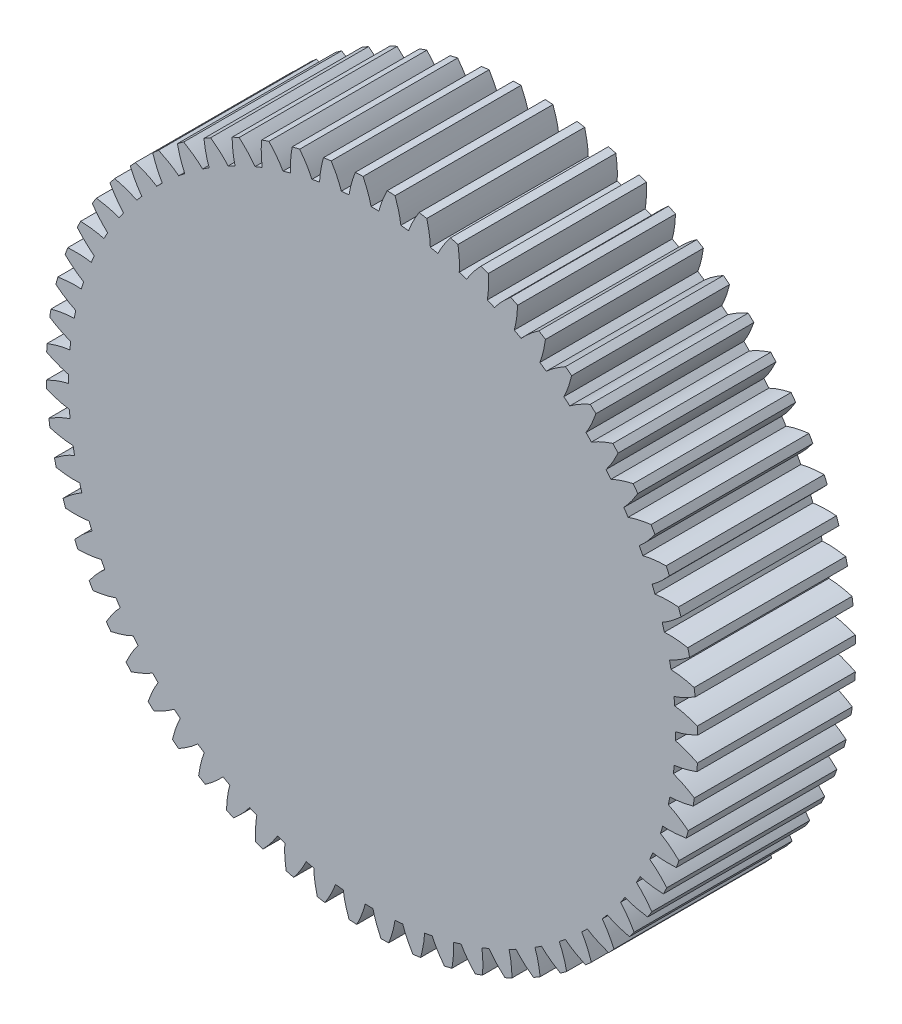
SolidWorks part; units mm, degrees
note: '?' marks a value the reader was unsure of.
ref_plane "Front" through (0, 0, 0) normal (0, 0, 1) x (1, 0, 0)
ref_plane "Top" through (0, 0, 0) normal (0, 1, 0) x (1, 0, 0)
ref_plane "Right" through (0, 0, 0) normal (1, 0, 0) x (0, 0, -1)
ref_axis "Axis1" through (0, 0, -80.9) along (0, 0, 1)?
sketch "Sketch1" plane through (0, 0, 0) normal (0, 0, 1) x (1, 0, 0)
  circle A0 centre (0, 0) radius 26.1937
  dimension "D1" = 52.3875
extrude "Boss-Extrude1" add sketch "Sketch1" against normal blind 12.7
sketch "Sketch2" plane through (0, 0, 0) normal (0, 0, 1) x (1, 0, 0)
  line L0 (12.2039, 0) -> (23.8682, 0)
  line L1 (0, 0) -> (-7.9817, 0.0769) construction
  line L2 (12.2016, -0.2353) -> (23.8638, -0.4601)
  circle A0 centre (0, 0) radius 25.4 construction
  circle A1 centre (0, 0) radius 23.8682 construction
  circle A2 centre (0, 0) radius 24.4078 construction
  arc A3 (12.2016, -0.2353) -> (12.2039, 0) centre (0, 0) ccw
  spline S0 degree 4 poles (23.8682, 0) (23.905, 0.0012) (23.9784, 0.0057) (24.1835, 0.03) (24.5698, 0.1058) (25.1502, 0.2727) (25.9221, 0.5776) (26.8744, 1.0589) (27.9314, 1.7266) (29.0206, 2.5635) (30.1105, 3.5653) (31.1179, 4.6498) (32.0445, 5.8037) (32.9341, 7.0767) (33.9284, 8.7227) (34.9504, 10.777) (35.9105, 13.2637) (36.6996, 16.1187) (37.2234, 19.0334) (37.4944, 21.9819) (37.5245, 24.9424) (37.3256, 27.8961) (36.9613, 30.4603) (36.5566, 32.4541) (36.2047, 33.8902) (35.9161, 34.9617) (35.6044, 36.0247) (35.2615, 37.0827) (34.8932, 38.1244) (34.5635, 38.9946) (34.2959, 39.6709) (34.0281, 40.3138) (33.8041, 40.8352) (33.5399, 41.426) (33.3651, 41.8069) (33.077, 42.4195) (32.8445, 42.8918) (32.5584, 43.4637) (32.2947, 43.9691) (32.0061, 44.5115) (31.7241, 45.0221) (31.4994, 45.421) (31.353, 45.6739) (31.277, 45.8051) knots 0 0 0 0 0 0.002802 0.005604 0.015718 0.02996 0.048734 0.068727 0.096889 0.125051 0.153212 0.181374 0.209535 0.237696 0.271429 0.327752 0.384075 0.440398 0.496721 0.553044 0.609367 0.66569 0.722013 0.750174 0.764255 0.778336 0.806497 0.834659 0.84874 0.86282 0.876901 0.890982 0.900036 0.909091 0.920455 0.931818 0.943182 0.954545 0.965909 0.977273 0.988636 1 1 1 1 1 construction
  spline S1 degree 4 poles (23.8682, 0) (23.905, 0.0012) (23.9784, 0.0057) (24.1835, 0.03) (24.5698, 0.1058) (25.1502, 0.2727) (25.9221, 0.5776) (26.8744, 1.0589) (27.9314, 1.7266) (29.0206, 2.5635) (30.1105, 3.5653) (31.1179, 4.6498) (32.0445, 5.8037) (32.9341, 7.0767) (33.9284, 8.7227) (34.9504, 10.777) (35.9105, 13.2637) (36.6996, 16.1187) (37.2234, 19.0334) (37.4944, 21.9819) (37.5245, 24.9424) (37.3256, 27.8961) (36.9613, 30.4603) (36.5566, 32.4541) (36.2047, 33.8902) (35.9161, 34.9617) (35.6044, 36.0247) (35.2615, 37.0827) (34.8932, 38.1244) (34.5635, 38.9946) (34.2959, 39.6709) (34.0281, 40.3138) (33.8041, 40.8352) (33.6088, 41.2719) (33.5189, 41.4704) (33.4739, 41.5686) knots 0 0 0 0 0 0.002802 0.005604 0.015718 0.02996 0.048734 0.068727 0.096889 0.125051 0.153212 0.181374 0.209535 0.237696 0.271429 0.327752 0.384075 0.440398 0.496721 0.553044 0.609367 0.66569 0.722013 0.750174 0.764255 0.778336 0.806497 0.834659 0.84874 0.86282 0.876901 0.890982 0.900036 0.909091 0.909091 0.909091 0.909091 0.909091
  spline S2 degree 4 poles (23.8638, -0.4601) (23.9005, -0.462) (23.9738, -0.468) (24.1784, -0.4962) (24.5632, -0.5794) (25.1403, -0.7574) (25.9062, -1.0772) (26.849, -1.5767) (27.8929, -2.2647) (28.9658, -3.1224) (30.0362, -4.1451) (31.0225, -5.2488) (31.9267, -6.4204) (32.7915, -7.7102) (33.7539, -9.3751) (34.7362, -11.4487) (35.6481, -13.9535) (36.382, -16.8231) (36.8496, -19.7474) (37.0636, -22.7006) (37.0367, -25.6611) (36.7809, -28.6104) (36.3672, -31.1671) (35.9242, -33.1528) (35.5446, -34.5818) (35.2354, -35.6476) (34.9033, -36.7044) (34.5401, -37.7555) (34.1518, -38.7899) (33.8053, -39.6537) (33.5248, -40.3246) (33.2446, -40.9622) (33.0106, -41.4793) (32.7351, -42.0649) (32.553, -42.4423) (32.2531, -43.0492) (32.0116, -43.517) (31.7145, -44.0833) (31.4411, -44.5835) (31.1421, -45.1202) (30.8503, -45.6253) (30.618, -46.0198) (30.4667, -46.2698) (30.3882, -46.3995) knots 0 0 0 0 0 0.002802 0.005604 0.015718 0.02996 0.048734 0.068727 0.096889 0.125051 0.153212 0.181374 0.209535 0.237696 0.271429 0.327752 0.384075 0.440398 0.496721 0.553044 0.609367 0.66569 0.722013 0.750174 0.764255 0.778336 0.806497 0.834659 0.84874 0.86282 0.876901 0.890982 0.900036 0.909091 0.920455 0.931818 0.943182 0.954545 0.965909 0.977273 0.988636 1 1 1 1 1 construction
  spline S3 degree 4 poles (23.8638, -0.4601) (23.9005, -0.462) (23.9738, -0.468) (24.1784, -0.4962) (24.5632, -0.5794) (25.1403, -0.7574) (25.9062, -1.0772) (26.849, -1.5767) (27.8929, -2.2647) (28.9658, -3.1224) (30.0362, -4.1451) (31.0225, -5.2488) (31.9267, -6.4204) (32.7915, -7.7102) (33.7539, -9.3751) (34.7362, -11.4487) (35.6481, -13.9535) (36.382, -16.8231) (36.8496, -19.7474) (37.0636, -22.7006) (37.0367, -25.6611) (36.7809, -28.6104) (36.3672, -31.1671) (35.9242, -33.1528) (35.5446, -34.5818) (35.2354, -35.6476) (34.9033, -36.7044) (34.5401, -37.7555) (34.1518, -38.7899) (33.8053, -39.6537) (33.5248, -40.3246) (33.2446, -40.9622) (33.0106, -41.4793) (32.807, -41.9121) (32.7132, -42.1088) (32.6663, -42.2062) knots 0 0 0 0 0 0.002802 0.005604 0.015718 0.02996 0.048734 0.068727 0.096889 0.125051 0.153212 0.181374 0.209535 0.237696 0.271429 0.327752 0.384075 0.440398 0.496721 0.553044 0.609367 0.66569 0.722013 0.750174 0.764255 0.778336 0.806497 0.834659 0.84874 0.86282 0.876901 0.890982 0.900036 0.909091 0.909091 0.909091 0.909091 0.909091
  dimension "D1" = 50.8
  dimension "D2" = 47.7364
  dimension "D3" = 48.8156
  dimension "D5" = 24.4078
  dimension "D4" = 0.552
extrude "Cut-Extrude1" cut sketch "Sketch2" against normal through all and the other way through all
pattern_circular "CirPattern1" count 64 over 360 about axis through (0, 0, -12.7) along (0, 0, 1) of "Cut-Extrude1"
sketch "Sketch3" plane through (0, 0, 0) normal (0, 0, 1) x (1, 0, 0)
  circle A1 centre (0, 0) radius 24.4078 construction
  circle A2 centre (0, 0) radius 24.4078
extrude "Boss-Extrude2" add sketch "Sketch3" against normal up to surface (12.7 mm away) up to face at (0, 0, -12.7)
sketch "Sketch4" plane through (0, 0, 0) normal (0, 0, 1) x (1, 0, 0)
  circle A0 centre (0, 0) radius 25.4 construction
  circle A1 centre (0, 0) radius 25.4
surface "Pitch Circle" sketch "Sketch4"
equation "\"P\"= \"P0\"'Diametral Pitch"
equation "\"N\"= \"N0\"'Number of Teeth"
equation "\"phi\"= \"phi0\"'Pressure Angle"
equation "\"a\"= 1 / \"P\"'Addendum"
equation "\"b\"= 1.25 / \"P\"'Dedendum"
equation "\"c\"= \"b\" - \"a\"'Clearance"
equation "\"dp\"= \"N\" / \"P\"'Pitch Circle Diameter"
equation "\"db\"= \"dp\" * cos ( \"phi\" )'Base Circle Diameter"
equation "\"alpha\"= sqr ( \"dp\" ^ 2 - \"db\" ^ 2 ) / \"db\" * 180deg / pi - \"phi\""
equation "\"D1@Sketch1\"=\"dp\"+2*\"a\""
equation "\"D3@Sketch2\"=\"dp\"-2*\"b\""
equation "\"D1@Sketch2\"=\"dp\""
equation "\"D2@Sketch2\"=\"db\""
equation "\"D4@Sketch2\"=360 / ( 4 * \"N\" ) - \"alpha\""
equation "\"D5@Sketch2\"=(\"dp\"-2*\"b\")/2"
equation "\"D1@CirPattern1\"=\"N\""
